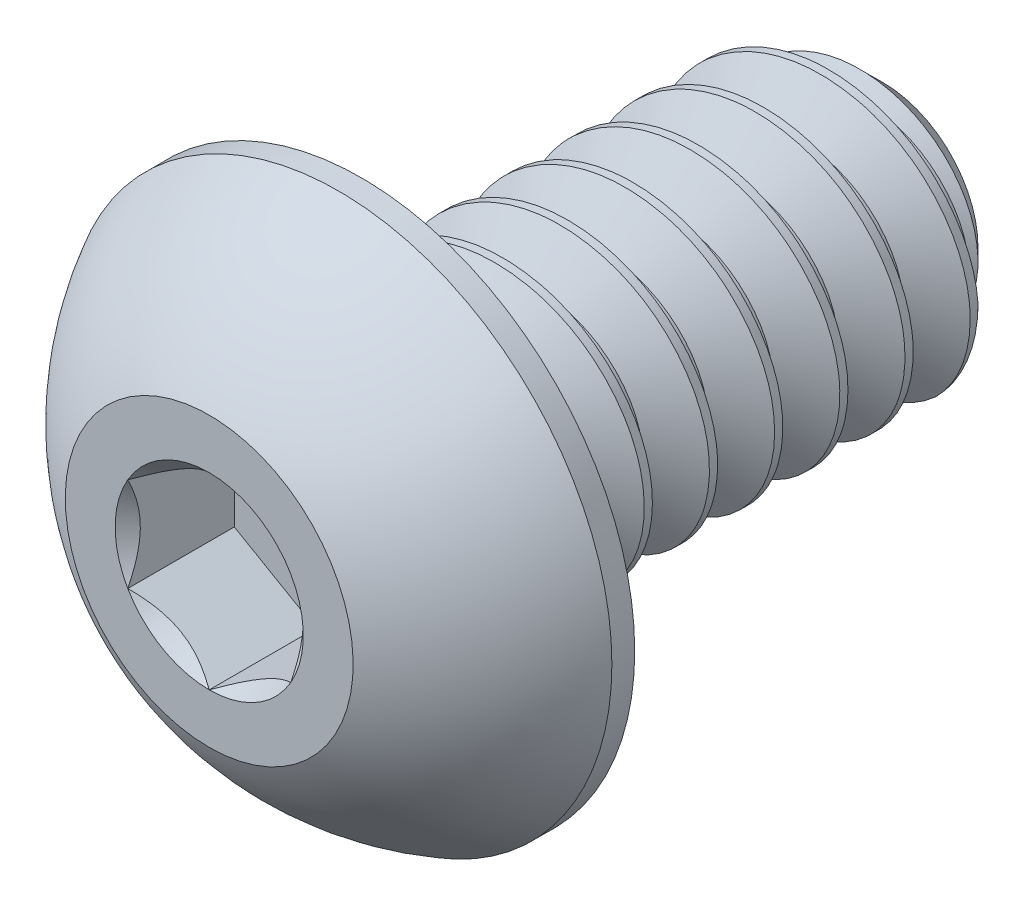
SolidWorks part; units mm, degrees
material "AISI 316 Annealed Stainless Steel Bar (SS)"
ref_plane "Front" through (0, 0, 0) normal (0, 0, 1) x (1, 0, 0)
ref_plane "Top" through (0, 0, 0) normal (0, 1, 0) x (1, 0, 0)
ref_plane "Right" through (0, 0, 0) normal (1, 0, 0) x (0, 0, -1)
sketch "Sketch1" plane through (0, 0, 0) normal (1, 0, 0) x (0, 0, -1)
  line L2 (1.8542, 1.7526) -> (8.2042, 1.7526)
  line L3 (8.2042, 1.7526) -> (8.2042, 0)
  line L4 (8.2042, 0) -> (1.8542, 0)
  line L6 (1.5761, 3.3274) -> (1.8542, 3.3274) construction
  line L7 (8.2042, 1.7526) -> (8.2042, -1.7526) construction
  line L8 (0, 0) -> (1.8542, 0) construction
  line L9 (1.8542, 3.3274) -> (1.8542, -3.3274) construction
  line L11 (1.8542, 1.7526) -> (1.8542, 0)
  line L13 (0, 0.9922) -> (0, -0.9922) construction
  line L14 (0, 0.9922) -> (0, 1.7526) construction
  arc A3 (0, 1.7526) -> (1.5761, 3.3274) centre (3.326, 0) cw construction
  dimension "D1" = 0.2781
revolve "Revolve1" add sketch "Sketch1" angle 360 mid plane about L4
sketch "Sketch3" plane through (0, 0, -8.2042) normal (0, 0, -1) x (-1, 0, 0)
  circle A0 centre (0, 0) radius 1.7526
curve "Helix/Spiral1" pitch 0.7937 height 7.1437 radius 1.7526 centre (0, 0, -8.2042) axis (0, 0, 1) start towards (0, 1, 0)
sketch "Sketch2" plane through (0, 0, 0) normal (1, 0, 0) x (0, 0, -1)
  line L0 (8.2042, 1.7526) -> (8.8987, 1.7526)
  line L1 (8.8987, 1.7526) -> (8.6011, 1.237)
  line L2 (8.6011, 1.237) -> (8.5019, 1.237)
  line L3 (8.5019, 1.237) -> (8.2042, 1.7526)
  line L4 (8.353, 1.4948) -> (8.7499, 1.4948) construction
  dimension "D1" = 60
  dimension "D2" = 0.0992
  dimension "D3" = 0.3969
chamfer "Chamfer1" distance 0.5953 angle 45 1 edges at (0, 1.7526, -8.2042)
sweep "Cut-Sweep1" cut profiles "Sketch2" path "Helix/Spiral1" align with end faces yes
sketch "Sketch7" plane through (0, 0, 0) normal (1, 0, 0) x (0, 0, -1)
  line L6 (1.5761, 3.3274) -> (1.8542, 3.3274) construction
  line L8 (0, 0) -> (1.8542, 0) construction
  line L11 (1.8542, 3.3274) -> (1.8542, -3.3274) construction
  line L12 (1.5761, 3.3274) -> (1.8542, 3.3274)
  line L13 (0, 0) -> (1.8542, 0)
  line L14 (0, 0.9922) -> (0, -0.9922) construction
  line L15 (1.8542, 3.3274) -> (1.8542, 0)
  line L16 (0, 1.7526) -> (0, 0)
  arc A2 (1.5761, 3.3274) -> (0, 1.7526) centre (3.326, 0) ccw construction
  arc A3 (1.5761, 3.3274) -> (0, 1.7526) centre (3.326, 0) ccw
revolve "Revolve2" add sketch "Sketch7" angle 360 mid plane about L13
sketch "Sketch5" plane through (0, 0, 0) normal (0, 0, 1) x (1, 0, 0)
  line L1 (0.9922, -0.5728) -> (0.9922, 0.5728)
  line L2 (0.9922, 0.5728) -> (0, 1.1457)
  line L3 (0, 1.1457) -> (-0.9922, 0.5728)
  line L4 (-0.9922, 0.5728) -> (-0.9922, -0.5728)
  line L5 (-0.9922, -0.5728) -> (0, -1.1457)
  line L6 (0, -1.1457) -> (0.9922, -0.5728)
  circle A0 centre (0, 0) radius 0.9922 construction
extrude "Cut-Extrude2" cut sketch "Sketch5" against normal blind 1.2979
sketch "Sketch6" plane through (0, 0, 0) normal (0, 0, 1) x (1, 0, 0)
  circle A0 centre (0, 0) radius 1.1457
extrude "Cut-Extrude3" cut sketch "Sketch6" against normal blind 1.2979 draft 45
sketch "Sketch9" [suppressed] plane through (0, 0, -1.4986) normal (0, 0, 1) x (1, 0, 0)
  circle A2 centre (0, 0) radius 1.4224
extrude "Boss-Extrude2" [suppressed] add sketch "Sketch9" against normal offset from surface (6.35 mm away) 28.575 up to face at (0, 1.1573, -8.2042)
sketch "Sketch10" plane through (0, 0, 0) normal (1, 0, 0) x (0, 0, -1)
  line L0 (8.2042, 1.7526) -> (8.2042, -1.7526) construction
  point P0 (7.0136, -1.7526)
  dimension "D1" = 1.1906
equation "\"D3@Helix/Spiral1\" = \"Lg@Sketch1\" + \"D4@Helix/Spiral1\""
equation "\"D2@Sketch2\" = \"D4@Helix/Spiral1\" * .125"
equation "\"D3@Sketch2\" = \"D4@Helix/Spiral1\" * .5"
equation "\"D1@Chamfer1\" = \"D4@Helix/Spiral1\" * .75"
equation "\"D1@Cut-Extrude2\" = \"Head Ht@Sketch1\" * .7"
equation "\"D1@Sketch1\" = \"Head Ht@Sketch1\" * .15"
equation "\"D1@Sketch10\" = \"D4@Helix/Spiral1\" * 1.5"
equation "\"D1@Cut-Extrude3\" = \"D1@Cut-Extrude2\""
